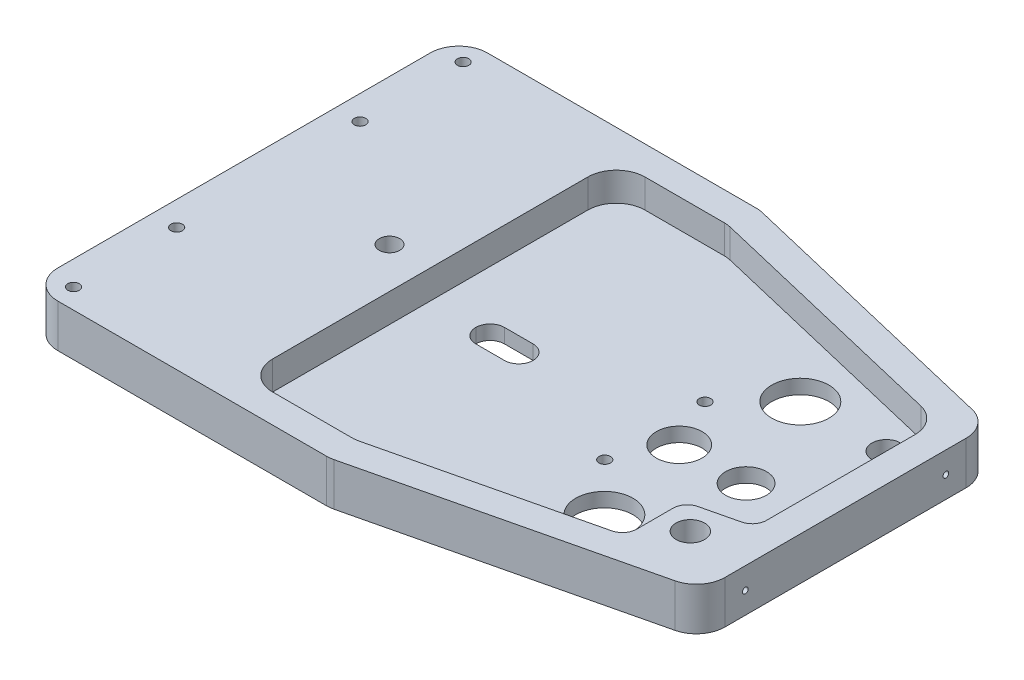
SolidWorks part; units mm, degrees
material "Carvalho"
ref_plane "Plano frontal" through (0, 0, 0) normal (0, 0, 1) x (1, 0, 0)
ref_plane "Plano superior" through (0, 0, 0) normal (0, 1, 0) x (1, 0, 0)
ref_plane "Plano direito" through (0, 0, 0) normal (1, 0, 0) x (0, 0, -1)
sketch "Esboço1" plane through (0, 0, 0) normal (0, 1, 0) x (1, 0, 0)
  line L0 (210, 50) -> (105, 75)
  line L1 (0, -75) -> (105, -75)
  line L2 (0, -75) -> (0, 75)
  line L3 (0, 75) -> (105, 75)
  line L4 (210, -50) -> (210, 50)
  line L7 (105, -75) -> (210, -50)
  line L8 (-14.8259, 0) -> (14.392, 0) construction
  line L9 (0, 21.2472) -> (0, -16.7598) construction
  circle A0 centre (50.8, 0) radius 3.5719
  circle A1 centre (175.26, 0) radius 7.14
  circle A2 centre (151.92, 0) radius 8
  circle A3 centre (151.92, 0) radius 8 construction
  circle A4 centre (8.5, -68) radius 2
  circle A5 centre (8.5, -32) radius 2
  circle A6 centre (8.5, -68) radius 2 construction
  circle A7 centre (8.5, -32) radius 2 construction
  circle A8 centre (8.5, 32) radius 2
  circle A9 centre (8.5, 68) radius 2
  point P0 (0, 0)
  dimension "D3" = 7.1437
  dimension "D5" = 14.28
  dimension "D1" = 25
  dimension "D2" = 150
  dimension "D4" = 50.8
  dimension "D6" = 210
  dimension "D7" = 175.26
  dimension "D8" = 105
extrude "Ressalto-extrusão1" add sketch "Esboço1" along normal blind 15
sketch "Esboço2" plane through (210, 0, 0) normal (1, 0, 0) x (0, 0, -1)
  line L0 (0, 15) -> (0, 0) construction
  line L1 (-50, 15) -> (50, 15) construction
  circle A0 centre (35, 7.5) radius 1
  circle A1 centre (-35, 7.5) radius 1
  point P9 (0, 7.5)
  dimension "D1" = 2
  dimension "D2" = 35
extrude "Corte-extrusão1" cut sketch "Esboço2" against normal blind 10
sketch "Esboço3" plane through (0, 15, 0) normal (0, 1, 0) x (1, 0, 0)
  line L0 (200, 42.1014) -> (200, -42.1014)
  line L2 (65, -65) -> (65, 65)
  line L6 (210, -50) -> (210, 50) construction
  line L7 (0, 75) -> (0, -75) construction
  line L8 (-22.821, 0) -> (224.4652, 0) construction
  line L9 (65, 65) -> (103.8259, 65)
  line L10 (103.8259, 65) -> (200, 42.1014)
  line L11 (65, -65) -> (103.8259, -65)
  line L12 (103.8259, -65) -> (200, -42.1014)
  line L13 (105, -75) -> (210, -50) construction
  line L14 (0, -75) -> (105, -75) construction
  line L15 (180, -26.3042) -> (200, -21.5423)
  line L16 (180, -46.8633) -> (180, -26.3042)
  circle M12 centre (151.92, 0) radius 8
  circle M14 centre (175.26, 0) radius 7.14
  dimension "D1" = 10
  dimension "D2" = 65
  dimension "D3" = 10
  dimension "D4" = 10
  dimension "D5" = 20
  dimension "D6" = 20
extrude "Corte-extrusão2" cut sketch "Esboço3" against normal blind 10 contours L2 L8 L0 L10 L9 M12 M14 | L8 L2 L11 L12 L16 L15 L0 M14 M12 region at (122.8919, 15, 29.2811) region at (126.5743, 15, -29.5512)
fillet "Filete1" radius 10 11 edges at (105, 7.5, 75) (0, 7.5, 75) (0, 7.5, -75) (210, 7.5, 50) (105, 7.5, -75) (210, 7.5, -50) (200, 10, -42.1014) (103.8259, 10, 65) (65, 10, 65) (103.8259, 10, -65) (65, 10, -65)
sketch "Esboço5" plane through (0, 0, 0) normal (0, -1, 0) x (1, 0, 0)
  line L0 (175.26, 0) -> (90.92, 0) construction
  line L2 (143.42, 17.5) -> (143.42, -17.5) construction
  line L3 (175.26, 0) -> (101.1849, 0) construction
  line L8 (80.92, -5) -> (100.92, -5)
  line L9 (80.92, -5) -> (80.92, 5)
  line L10 (80.92, 5) -> (100.92, 5)
  line L11 (100.92, -5) -> (100.92, 5)
  line L12 (80.92, -5) -> (100.92, 5) construction
  line L13 (80.92, 5) -> (100.92, -5) construction
  circle A0 centre (143.42, 17.5) radius 2
  circle A1 centre (143.42, -17.5) radius 2
  point P5 (143.42, 0)
  dimension "D6" = 4
  dimension "D1" = 35
  dimension "D2" = 42.5
  dimension "D3" = 20
  dimension "D4" = 31.84
  dimension "D5" = 10
extrude "Corte-extrusão4" cut sketch "Esboço5" against normal through all
fillet "Filete2" radius 5 4 edges at (80.92, 2.5, -5) (80.92, 2.5, 5) (100.92, 2.5, 5) (100.92, 2.5, -5)
fillet "Filete3" radius 5 3 edges at (180, 10, 46.8633) (180, 10, 26.3042) (200, 10, 21.5423)
sketch "Esboço6" plane through (0, 15, 0) normal (0, 1, 0) x (1, 0, 0)
  line L0 (224.3981, 0) -> (150.0179, 0) construction
  circle A0 centre (190, -34.2028) radius 5
  circle A1 centre (190, 34.2028) radius 5
  circle A2 centre (160, 34.2028) radius 10
  arc A3 (200, 34.2028) -> (192.3162, 43.9309) centre (190, 34.2028) ccw construction
  circle A4 centre (160, -34.2028) radius 10
  point P9 (0, 0)
  point P10 (0, 0)
  dimension "D1" = 10
  dimension "D2" = 20
  dimension "D3" = 30
extrude "Corte-extrusão5" cut sketch "Esboço6" against normal through all
